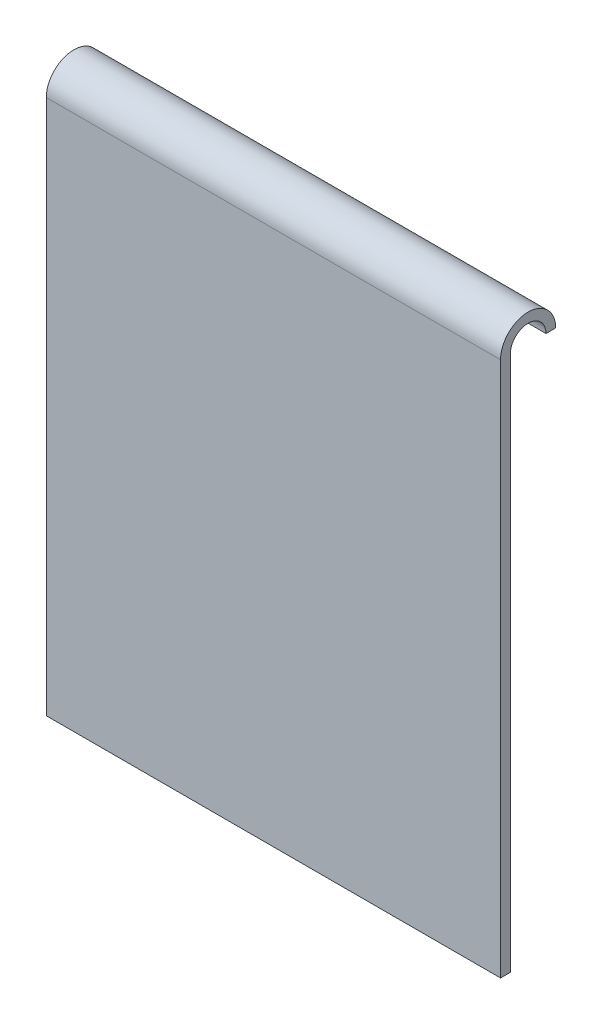
SolidWorks part; units mm, degrees
ref_plane "前基準面" through (0, 0, 0) normal (0, 0, 1) x (1, 0, 0)
ref_plane "上基準面" through (0, 0, 0) normal (0, 1, 0) x (1, 0, 0)
ref_plane "右基準面" through (0, 0, 0) normal (1, 0, 0) x (0, 0, -1)
sketch "草圖1" plane through (0, 0, 0) normal (1, 0, 0) x (0, 0, -1)
  line L0 (-2.55, -4) -> (-2.55, -20.5)
  line L1 (-2.55, -20.5) -> (-2.25, -20.5)
  line L2 (-2.25, -20.5) -> (-2.25, -4)
  line L3 (-1.15, -4) -> (-0.85, -4)
  arc A0 (-0.85, -4) -> (-2.55, -4) centre (-1.7, -4) ccw
  arc A1 (-2.25, -4) -> (-1.15, -4) centre (-1.7, -4) cw
extrude "填料-伸長1" add sketch "草圖1" along normal blind 7 and the other way blind 7
